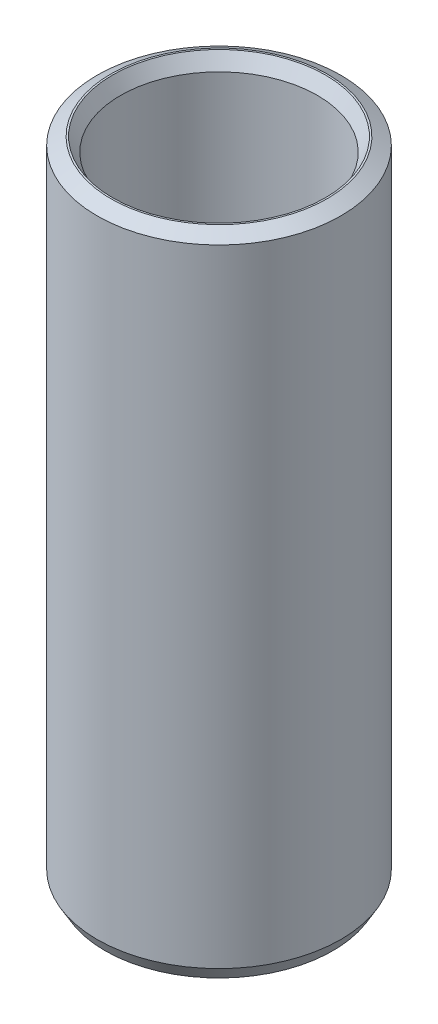
SolidWorks part; units mm, degrees
ref_plane "Front Plane" through (0, 0, 0) normal (0, 0, 1) x (1, 0, 0)
ref_plane "Top Plane" through (0, 0, 0) normal (0, 1, 0) x (1, 0, 0)
ref_plane "Right Plane" through (0, 0, 0) normal (1, 0, 0) x (0, 0, -1)
sketch "Sketch1" plane through (0, 0, 0) normal (0, 1, 0) x (1, 0, 0)
  circle A0 centre (0, 0) radius 37.5
  dimension "SLEEVE_OD" = 75
extrude "Boss-Extrude1" add sketch "Sketch1" along normal blind 199.475
sketch "Sketch2" plane through (0, 0, 0) normal (0, 1, 0) x (1, 0, 0)
  circle A0 centre (0, 0) radius 30.2947
  dimension "BORE_D" = 60.5893
extrude "Cut-Extrude1" cut sketch "Sketch2" along normal through all
chamfer "Chamfer1" distance 2.4413 angle 60 4 edges at (0, 199.475, 30.2947) (0, 0, 30.2947) (0, 0, 37.5) (0, 199.475, 37.5) first distance on face at (0, 199.475, 30.2947) first distance on face at (0, 0, 30.2947) first distance on face at (0, 199.475, 37.5)
